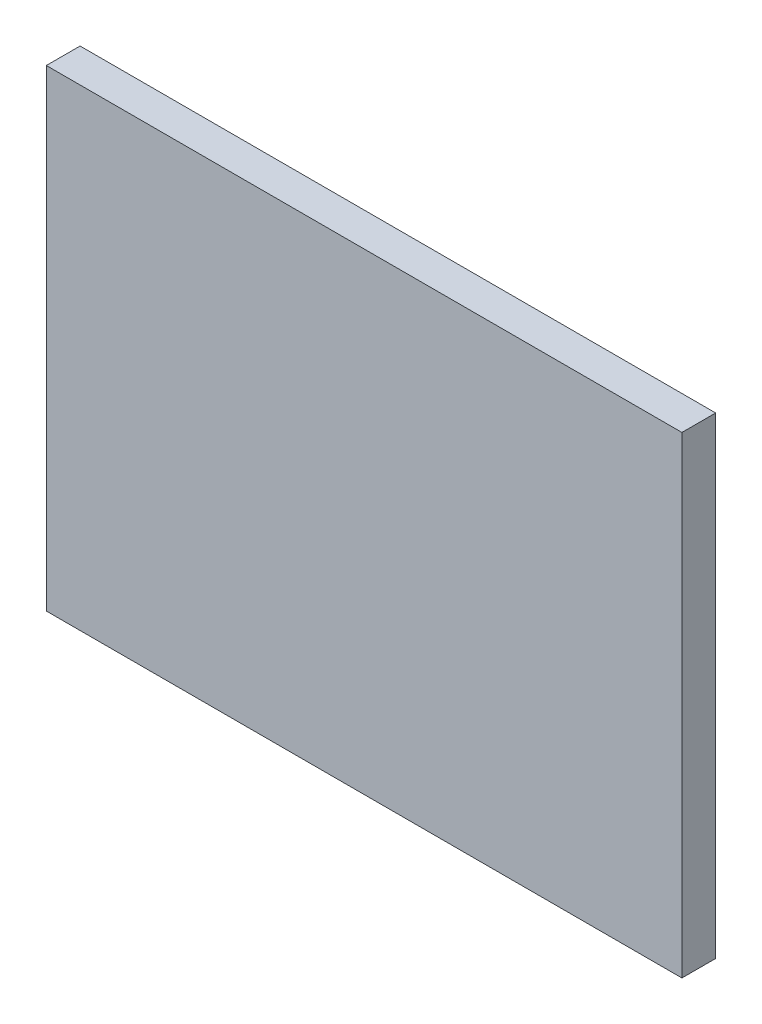
SolidWorks part; units mm, degrees
material "Pine"
ref_plane "Front Plane" through (0, 0, 0) normal (0, 0, 1) x (1, 0, 0)
ref_plane "Top Plane" through (0, 0, 0) normal (0, 1, 0) x (1, 0, 0)
ref_plane "Right Plane" through (0, 0, 0) normal (1, 0, 0) x (0, 0, -1)
sketch "Sketch1" plane through (0, 0, 0) normal (0, 0, 1) x (1, 0, 0)
  line L0 (-5300.6625, 1520.825) -> (-5451.475, 1520.825)
  line L1 (-5456.2375, 1384.3) -> (-5456.2375, 1516.0625)
  line L2 (-5557.8375, 1546.225) -> (-5194.3, 1546.225)
  line L3 (-5557.8375, 1539.875) -> (-5194.3, 1539.875)
  line L4 (-5297.4875, 1377.95) -> (-5454.65, 1377.95)
  line L5 (-5291.1375, 1384.3) -> (-5291.1375, 1516.0625)
  line L6 (-5300.6625, 1525.5875) -> (-5451.475, 1525.5875)
  line L7 (-5461, 1384.3) -> (-5461, 1516.0625)
  line L8 (-5297.4875, 1382.7125) -> (-5454.65, 1382.7125)
  line L9 (-5295.9, 1384.3) -> (-5295.9, 1516.0625)
  line L10 (-5740.4, 998.5375) -> (-5740.4, 1181.1)
  line L11 (-5740.4, 1181.1) -> (-5512.5938, 1181.1)
  line L12 (-5512.5938, 1181.1) -> (-5512.5938, 998.5375)
  line L13 (-5512.5938, 998.5375) -> (-5740.4, 998.5375)
  line L14 (-5258.5938, 1181.1) -> (-5486.4, 1181.1)
  line L15 (-5258.5938, 998.5375) -> (-5258.5938, 1181.1)
  line L16 (-5486.4, 998.5375) -> (-5258.5938, 998.5375)
  line L17 (-5486.4, 1181.1) -> (-5486.4, 998.5375)
  line L18 (-5740.4, 898.525) -> (-5011.7375, 898.525)
  line L19 (-5168.1062, 1384.3) -> (-5168.1062, 1392.2375)
  line L20 (-5176.0437, 1400.175) -> (-5245.8937, 1400.175)
  line L21 (-5253.8313, 1392.2375) -> (-5253.8313, 1384.3)
  line L22 (-5451.475, 1512.8875) -> (-5451.475, 1384.3)
  line L23 (-5303.8375, 1516.0625) -> (-5448.3, 1516.0625)
  line L24 (-5498.3062, 1384.3) -> (-5451.475, 1384.3)
  line L25 (-5253.8313, 1384.3) -> (-5300.6625, 1384.3)
  line L26 (-5584.0312, 1384.3) -> (-5740.4, 1384.3)
  line L27 (-5564.1875, 1536.7) -> (-5740.4, 1536.7)
  line L28 (-5740.4, 1357.3125) -> (-5740.4, 1206.5)
  line L29 (-5011.7375, 1357.3125) -> (-5740.4, 1357.3125)
  line L30 (-5011.7375, 1206.5) -> (-5011.7375, 1357.3125)
  line L31 (-5740.4, 1206.5) -> (-5011.7375, 1206.5)
  line L32 (-4765.675, 1549.4) -> (-4978.4, 1549.4)
  line L33 (-4765.675, 1397) -> (-4765.675, 1549.4)
  line L34 (-4978.4, 1397) -> (-4765.675, 1397)
  line L35 (-4978.4, 1549.4) -> (-4978.4, 1397)
  line L36 (-4765.675, 1371.6) -> (-4978.4, 1371.6)
  line L37 (-4765.675, 1219.2) -> (-4765.675, 1371.6)
  line L38 (-4978.4, 1219.2) -> (-4765.675, 1219.2)
  line L39 (-4978.4, 1371.6) -> (-4978.4, 1219.2)
  line L40 (-5284.7875, 803.275) -> (-5272.0875, 803.275)
  line L41 (-5187.95, 1536.7) -> (-5011.7375, 1536.7)
  line L42 (-5300.6625, 1384.3) -> (-5300.6625, 1512.8875)
  line L43 (-5740.4, 1536.7) -> (-5740.4, 1384.3)
  line L44 (-5557.8375, 1536.7) -> (-5557.8375, 1549.4)
  line L45 (-5557.8375, 1549.4) -> (-5194.3, 1549.4)
  line L46 (-5194.3, 1549.4) -> (-5194.3, 1536.7)
  line L47 (-5011.7375, 1536.7) -> (-5011.7375, 1384.3)
  line L48 (-5011.7375, 1384.3) -> (-5168.1062, 1384.3)
  line L49 (-5498.3062, 1384.3) -> (-5498.3062, 1392.2375)
  line L50 (-5506.2437, 1400.175) -> (-5576.0938, 1400.175)
  line L51 (-5584.0312, 1392.2375) -> (-5584.0312, 1384.3)
  line L52 (-5740.4, 660.4) -> (-5740.4, 898.525)
  line L53 (-5011.7375, 898.525) -> (-5011.7375, 660.4)
  line L54 (-5011.7375, 660.4) -> (-5740.4, 660.4)
  line L55 (-5291.1375, 803.275) -> (-5291.1375, 752.475)
  line L56 (-5265.7375, 752.475) -> (-5265.7375, 803.275)
  line L57 (-5284.7875, 752.475) -> (-5272.0875, 752.475)
  arc A0 (-5451.475, 1520.825) -> (-5456.2375, 1516.0625) centre (-5451.475, 1516.0625) ccw
  arc A1 (-5461, 1384.3) -> (-5454.65, 1377.95) centre (-5454.65, 1384.3) ccw
  arc A2 (-5297.4875, 1377.95) -> (-5291.1375, 1384.3) centre (-5297.4875, 1384.3) ccw
  circle A3 centre (-5037.9312, 1233.4875) radius 1.5875
  circle A4 centre (-5037.9312, 1328.7375) radius 1.5875
  circle A5 centre (-5714.2063, 1233.4875) radius 1.5875
  circle A6 centre (-5714.2063, 1328.7375) radius 1.5875
  circle A7 centre (-5018.0875, 1333.5) radius 1.5875
  circle A8 centre (-5018.0875, 1231.9) radius 1.5875
  circle A9 centre (-5734.05, 1231.9) radius 1.5875
  circle A10 centre (-5734.05, 1333.5) radius 1.5875
  circle A11 centre (-5734.05, 1511.3) radius 1.5875
  circle A12 centre (-5734.05, 1409.7) radius 1.5875
  circle A13 centre (-5018.0875, 1511.3) radius 1.5875
  circle A14 centre (-5018.0875, 1409.7) radius 1.5875
  arc A15 (-5557.8375, 1546.225) -> (-5557.8375, 1539.875) centre (-5557.8375, 1543.05) ccw
  arc A16 (-5194.3, 1539.875) -> (-5194.3, 1546.225) centre (-5194.3, 1543.05) ccw
  arc A17 (-5291.1375, 1516.0625) -> (-5300.6625, 1525.5875) centre (-5300.6625, 1516.0625) ccw
  arc A18 (-5451.475, 1525.5875) -> (-5461, 1516.0625) centre (-5451.475, 1516.0625) ccw
  arc A19 (-5456.2375, 1384.3) -> (-5454.65, 1382.7125) centre (-5454.65, 1384.3) ccw
  arc A20 (-5297.4875, 1382.7125) -> (-5295.9, 1384.3) centre (-5297.4875, 1384.3) ccw
  arc A21 (-5295.9, 1516.0625) -> (-5300.6625, 1520.825) centre (-5300.6625, 1516.0625) ccw
  circle A22 centre (-5702.3, 892.175) radius 1.5875
  circle A23 centre (-5734.05, 860.425) radius 1.5875
  circle A24 centre (-5474.8906, 892.175) radius 1.5875
  circle A25 centre (-5277.2469, 892.175) radius 1.5875
  circle A26 centre (-5049.8375, 892.175) radius 1.5875
  circle A27 centre (-5018.0875, 860.425) radius 1.5875
  circle A28 centre (-5296.6938, 1174.75) radius 1.5875
  circle A29 centre (-5448.3, 1174.75) radius 1.5875
  circle A30 centre (-5264.9437, 1155.7) radius 1.5875
  circle A31 centre (-5264.9437, 1023.9375) radius 1.5875
  circle A32 centre (-5518.9438, 1155.7) radius 1.5875
  circle A33 centre (-5518.9438, 1023.9375) radius 1.5875
  circle A34 centre (-5702.3, 1004.8875) radius 1.5875
  circle A35 centre (-5550.6937, 1004.8875) radius 1.5875
  arc A36 (-5576.0938, 1400.175) -> (-5584.0312, 1392.2375) centre (-5576.0938, 1392.2375) ccw
  arc A37 (-5168.1062, 1392.2375) -> (-5176.0437, 1400.175) centre (-5176.0437, 1392.2375) ccw
  arc A38 (-5245.8937, 1400.175) -> (-5253.8313, 1392.2375) centre (-5245.8937, 1392.2375) ccw
  arc A39 (-5448.3, 1516.0625) -> (-5451.475, 1512.8875) centre (-5448.3, 1512.8875) ccw
  arc A40 (-5284.7875, 803.275) -> (-5291.1375, 803.275) centre (-5287.9625, 803.275) ccw
  circle A41 centre (-5679.2812, 1026.3187) radius 1.5875
  circle A42 centre (-5679.2812, 1153.3187) radius 1.5875
  circle A43 centre (-5571.3313, 1153.3187) radius 1.5875
  circle A44 centre (-5571.3313, 1026.3187) radius 1.5875
  circle A45 centre (-5317.3312, 1153.3187) radius 1.5875
  circle A46 centre (-5317.3312, 1026.3187) radius 1.5875
  circle A47 centre (-5425.2812, 1026.3187) radius 1.5875
  circle A48 centre (-5425.2812, 1153.3187) radius 1.5875
  arc A49 (-5194.3, 1536.7) -> (-5187.95, 1536.7) centre (-5191.125, 1536.7) ccw
  arc A50 (-5564.1875, 1536.7) -> (-5557.8375, 1536.7) centre (-5561.0125, 1536.7) ccw
  arc A51 (-5300.6625, 1512.8875) -> (-5303.8375, 1516.0625) centre (-5303.8375, 1512.8875) ccw
  arc A52 (-5498.3062, 1392.2375) -> (-5506.2437, 1400.175) centre (-5506.2437, 1392.2375) ccw
  circle A53 centre (-5712.46, 784.225) radius 4.7625
  arc A54 (-5272.0875, 752.475) -> (-5265.7375, 752.475) centre (-5268.9125, 752.475) ccw
  arc A55 (-5291.1375, 752.475) -> (-5284.7875, 752.475) centre (-5287.9625, 752.475) ccw
  circle A56 centre (-5182.3938, 684.2125) radius 3.175
  circle A57 centre (-5239.5437, 684.2125) radius 3.175
  circle A58 centre (-5512.5938, 684.2125) radius 3.175
  circle A59 centre (-5569.7437, 684.2125) radius 3.175
  circle A60 centre (-5474.8906, 666.75) radius 1.5875
  circle A61 centre (-5277.2469, 666.75) radius 1.5875
  circle A62 centre (-5734.05, 698.5) radius 1.5875
  circle A63 centre (-5702.3, 666.75) radius 1.5875
  circle A64 centre (-5049.8375, 666.75) radius 1.5875
  circle A65 centre (-5018.0875, 698.5) radius 1.5875
  circle A66 centre (-5713.73, 835.025) radius 4.7625
  circle A67 centre (-5712.46, 819.785) radius 4.7625
  circle A68 centre (-5712.46, 802.005) radius 4.7625
  circle A69 centre (-5714.2063, 1314.45) radius 3.175
  circle A70 centre (-5037.9312, 1314.45) radius 3.175
  arc A71 (-5265.7375, 803.275) -> (-5272.0875, 803.275) centre (-5268.9125, 803.275) ccw
  ellipse E0 centre (-5371.3062, 1089.8188) end of major axis (-5277.6438, 1089.8188) minor radius 65.0875
  ellipse E1 centre (-5625.3062, 1089.8188) end of major axis (-5531.6438, 1089.8188) minor radius 65.0875
sketch "SideOutline" plane through (0, 0, 0) normal (0, 0, 1) x (1, 0, 0)
  line L0 (-4765.675, 1379.22) -> (-4765.675, 1219.2)
  line L1 (-4765.675, 1219.2) -> (-4980.94, 1219.2)
  line L2 (-4980.94, 1219.2) -> (-4980.94, 1379.22)
  line L3 (-4980.94, 1379.22) -> (-4765.675, 1379.22)
  line L8 (-4754.245, 1379.22) -> (-4982.0512, 1379.22) construction
extrude "SideOutline_Thickness" add sketch "SideOutline" against normal blind 11.43
